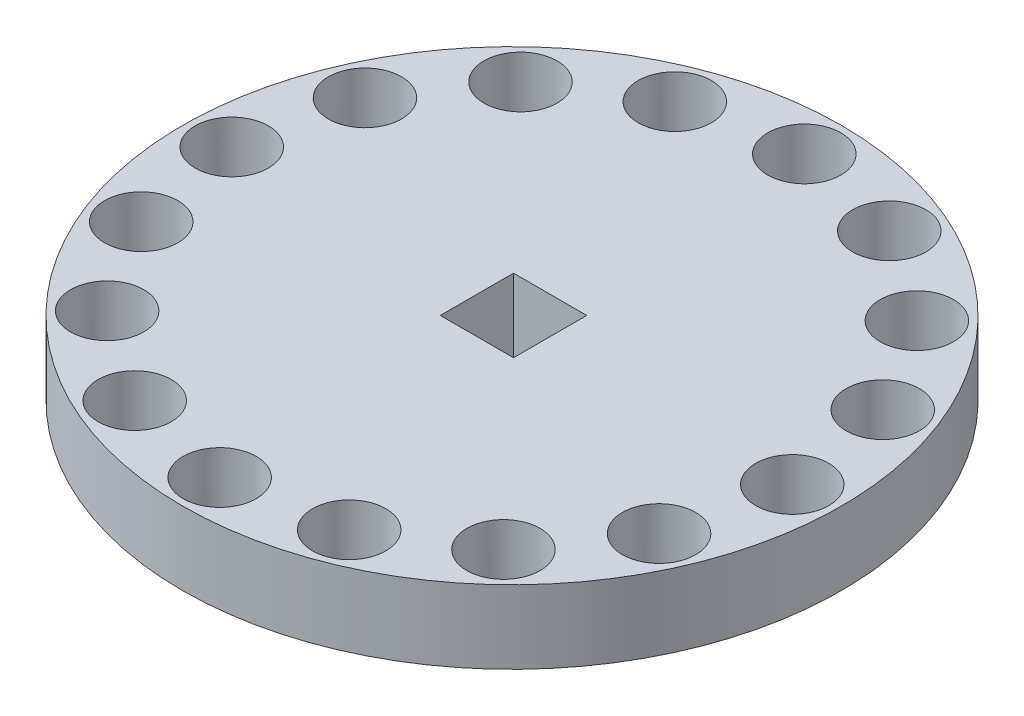
SolidWorks part; units mm, degrees
ref_plane "Ebene vorne" through (0, 0, 0) normal (0, 0, 1) x (1, 0, 0)
ref_plane "Ebene oben" through (0, 0, 0) normal (0, 1, 0) x (1, 0, 0)
ref_plane "Ebene rechts" through (0, 0, 0) normal (1, 0, 0) x (0, 0, -1)
sketch "Skizze1" plane through (0, 0, 0) normal (0, 1, 0) x (1, 0, 0)
  circle A0 centre (0, 0) radius 9
extrude "Aufsatz-Linear austragen1" add sketch "Skizze1" along normal blind 2
sketch "Skizze3" plane through (0, 2, 0) normal (0, 1, 0) x (1, 0, 0)
  line L0 (1.0142, 1.0274) -> (-0.9858, 1.0274)
  line L1 (1.0142, 1.0274) -> (1.0142, -0.9726)
  line L2 (1.0142, -0.9726) -> (-0.9858, -0.9726)
  line L3 (-0.9858, 1.0274) -> (-0.9858, -0.9726)
extrude "Schnitt-Linear austragen1" cut sketch "Skizze3" against normal blind 3
sketch "Skizze4" plane through (0, 2, 0) normal (0, 1, 0) x (1, 0, 0)
  circle A0 centre (7.818, -0.1647) radius 1
extrude "Schnitt-Linear austragen2" cut sketch "Skizze4" against normal blind 3
pattern_circular "Kreismuster1" count 16 over 360 about axis through (0, 2, 0) along (0, -1, 0) of "Schnitt-Linear austragen2"
